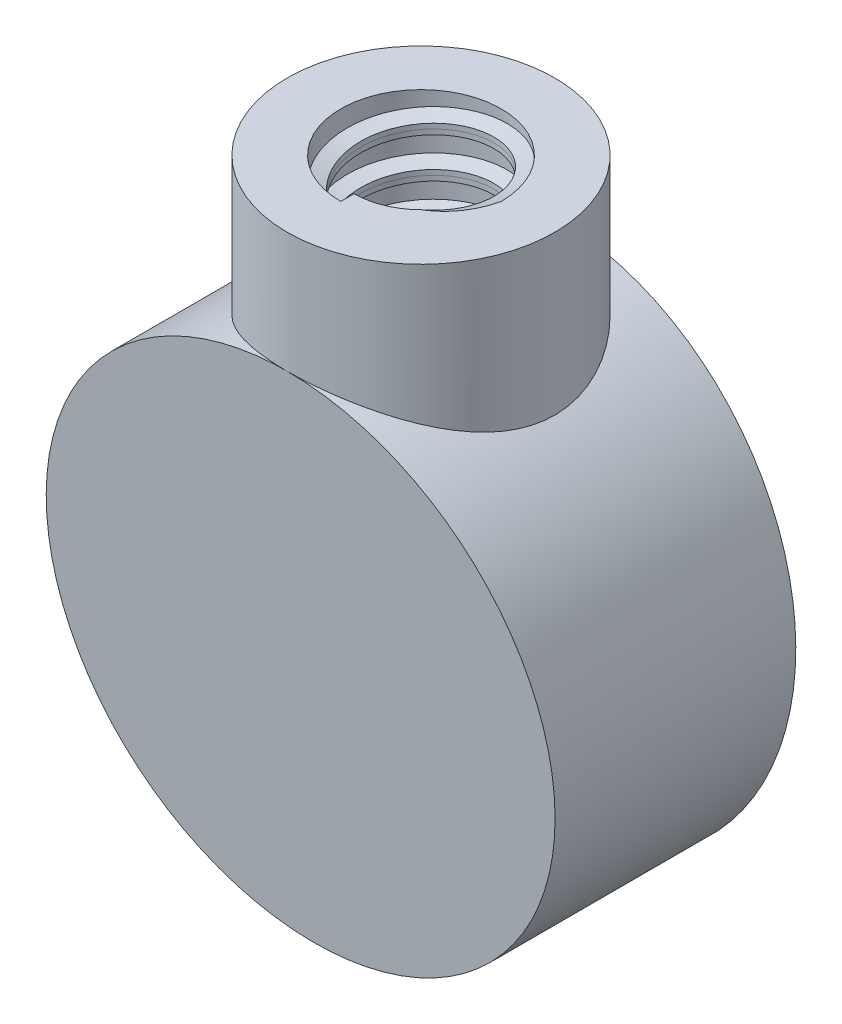
SolidWorks part; units mm, degrees
material "Latón"
ref_plane "Alzado" through (0, 0, 0) normal (0, 0, 1) x (1, 0, 0)
ref_plane "Planta" through (0, 0, 0) normal (0, 1, 0) x (1, 0, 0)
ref_plane "Vista lateral" through (0, 0, 0) normal (1, 0, 0) x (0, 0, -1)
sketch "Croquis1" plane through (0, 0, 0) normal (0, 0, 1) x (1, 0, 0)
  circle A0 centre (0, 0) radius 15.0812
  dimension "D1" = 30.1625
extrude "Saliente-Extruir1" add sketch "Croquis1" along normal blind 15.875
sketch "Croquis2" plane through (0, 0, 0) normal (0, 1, 0) x (1, 0, 0)
  circle A0 centre (0, -7.9375) radius 7.9375
extrude "Saliente-Extruir2" add sketch "Croquis2" along normal blind 22.225
sketch "Croquis3" plane through (0, 22.225, 0) normal (0, 1, 0) x (1, 0, 0)
  circle A0 centre (0, -7.9375) radius 4.7625
  dimension "D1" = 9.525
extrude "Cortar-Extruir1" cut sketch "Croquis3" against normal through all
sketch "Croquis4" plane through (0, 22.225, 0) normal (0, 1, 0) x (1, 0, 0)
  circle A0 centre (0, -7.9375) radius 4.7625
curve "Hélice/Espiral1" pitch 2.3813 height 35.7188 radius 4.7625 left hand yes centre (0, 22.225, 7.9375) axis (0, -1, 0) start towards (0, 0, 1)
sketch "Croquis5" plane through (0, 0, 0) normal (1, 0, 0) x (0, 0, -1)
  line L0 (-12.7, 22.225) -> (-12.7, 22.8203)
  line L1 (-12.7, 22.8203) -> (-11.9062, 22.5227)
  line L2 (-11.9062, 22.5227) -> (-11.9062, 22.225)
  line L3 (-3.175, 22.225) -> (-12.7, 22.225) construction
  line L4 (-11.9062, 22.225) -> (-11.9062, 21.9273)
  line L5 (-11.9062, 21.9273) -> (-12.7, 21.6297)
  line L6 (-12.7, 21.6297) -> (-12.7, 22.225)
  dimension "D1" = 0.7937
  dimension "D2" = 0.2977
  dimension "D3" = 0.5953
sweep "Barrer1" add profiles "Croquis5" path "Hélice/Espiral1"
sketch "Croquis6" plane through (0, 0, 0) normal (-1, 0, 0) x (0, 0, 1)
  line L0 (12.7, 22.225) -> (-7.5044, 22.225)
  line L1 (-7.5044, 22.8203) -> (-7.5044, 22.225)
  line L2 (-7.5044, 22.8203) -> (12.7, 22.8203)
  line L3 (12.7, 22.8203) -> (12.7, 22.225)
extrude "Cortar-Extruir2" cut sketch "Croquis6" against normal blind 6.858
ref_plane "Plano1" through (0, 0, 0) normal (1, 0, 0) x (0, 0, -1)
sketch "Croquis7" plane through (0, 0, 0) normal (1, 0, 0) x (0, 0, -1)
  line L0 (-15.875, 15.0812) -> (-15.875, -15.0812)
  line L1 (-15.875, -15.0812) -> (-14.2875, -15.0812)
  line L2 (-15.875, -15.0812) -> (-12.7, -15.0812) construction
  line L3 (-14.2875, -15.0812) -> (-15.875, 15.0812)
  line L4 (0, 15.0812) -> (0, -15.0812)
  line L5 (0, -15.0812) -> (0, 15.0812) construction
  line L6 (0, -15.0812) -> (-1.5875, -15.0812)
  line L7 (-1.5875, -15.0812) -> (0, 15.0812)
  dimension "D1" = 12.7
extrude "Cortar-Extruir3" cut sketch "Croquis7" against normal through all and the other way through all
